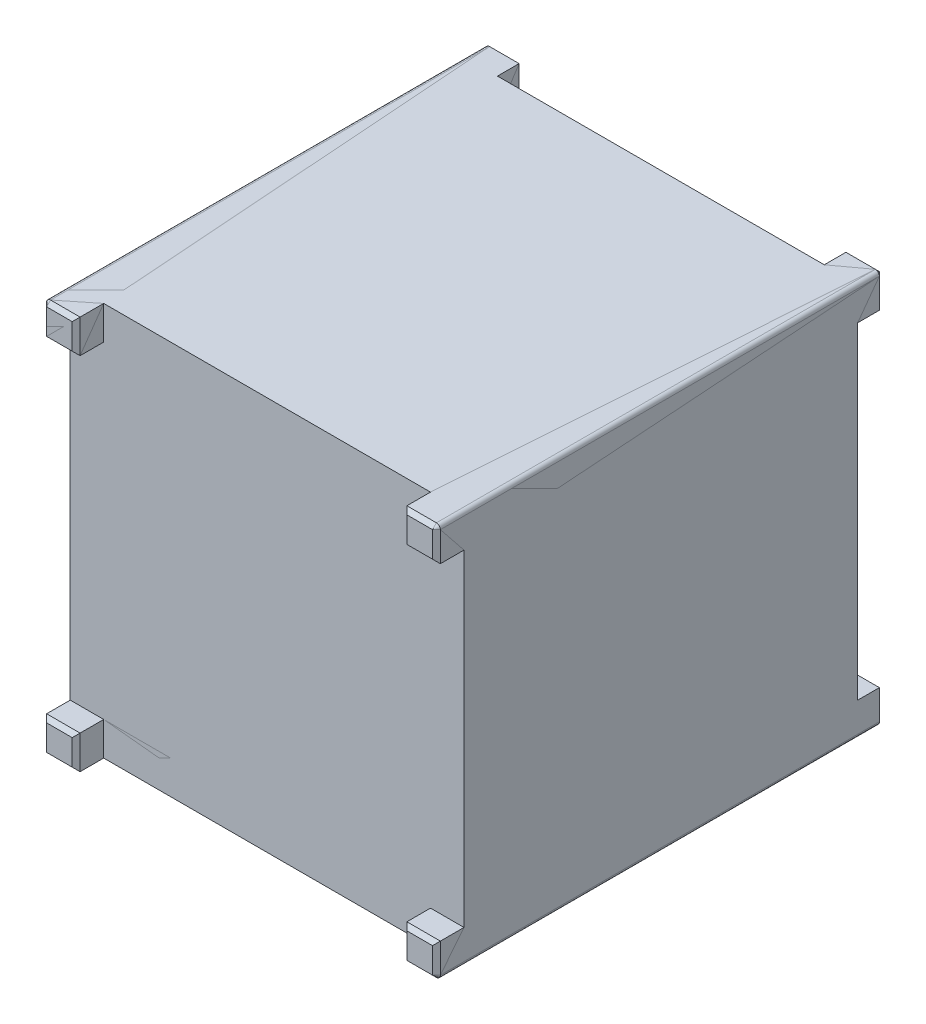
SolidWorks part; units mm, degrees
ref_plane "Front Plane" through (0, 0, 0) normal (0, 0, 1) x (1, 0, 0)
ref_plane "Top Plane" through (0, 0, 0) normal (0, 1, 0) x (1, 0, 0)
ref_plane "Right Plane" through (0, 0, 0) normal (1, 0, 0) x (0, 0, -1)
sketch "Sketch1" plane through (0, 0, 0) normal (0, 0, 1) x (1, 0, 0)
  line L1 (-50, -50) -> (50, -50) construction
  line L2 (-50, -50) -> (-50, 50) construction
  line L3 (-50, 50) -> (50, 50) construction
  line L4 (50, -50) -> (50, 50) construction
  line L5 (-50, -50) -> (50, 50) construction
  line L6 (-50, 50) -> (50, -50) construction
  line L23 (-50, 50) -> (-41.5, 50)
  line L24 (-50, 50) -> (-50, 41.5)
  line L25 (-50, 41.5) -> (-41.5, 41.5)
  line L26 (-41.5, 50) -> (-41.5, 41.5)
  line L27 (50, 50) -> (41.5, 50)
  line L28 (50, 50) -> (50, 41.5)
  line L29 (50, 41.5) -> (41.5, 41.5)
  line L30 (41.5, 50) -> (41.5, 41.5)
  line L31 (50, -50) -> (41.5, -50)
  line L32 (50, -50) -> (50, -41.5)
  line L33 (50, -41.5) -> (41.5, -41.5)
  line L34 (41.5, -50) -> (41.5, -41.5)
  line L35 (-50, -50) -> (-41.5, -50)
  line L36 (-50, -50) -> (-50, -41.5)
  line L37 (-50, -41.5) -> (-41.5, -41.5)
  line L38 (-41.5, -50) -> (-41.5, -41.5)
  point P0 (0, 0)
  dimension "D1" = 100
  dimension "D2" = 100
  dimension "D3" = 8.5
extrude "Boss-Extrude1" add sketch "Sketch1" along normal blind 56.75 and the other way blind 56.75
sketch "Sketch2" plane through (0, 0, 0) normal (0, 0, 1) x (1, 0, 0)
  line L1 (-50, -50) -> (50, -50)
  line L2 (-50, -50) -> (-50, 50)
  line L3 (-50, 50) -> (50, 50)
  line L4 (50, -50) -> (50, 50)
  line L5 (-50, -50) -> (50, 50) construction
  line L6 (-50, 50) -> (50, -50) construction
  point P0 (0, 0)
extrude "Boss-Extrude2" add sketch "Sketch2" along normal blind 49.75 and the other way blind 50.25
fillet "Fillet1" radius 1 4 edges at (50, -50, 0) (-50, -50, 0) (-50, 50, 0) (50, 50, 0)
chamfer "Chamfer2" distance 1 angle 45 40 edges at (-45.75, -41.5, 56.75) (-41.5, -45.75, 56.75) (-45.25, -50, 56.75) (-49.7071, -49.7071, 56.75) (-50, -45.25, 56.75) (41.5, -45.75, 56.75) (45.75, -41.5, 56.75) (50, -45.25, 56.75) (49.7071, -49.7071, 56.75) (45.25, -50, 56.75) (45.75, 41.5, 56.75) (41.5, 45.75, 56.75) (45.25, 50, 56.75) (49.7071, 49.7071, 56.75) (50, 45.25, 56.75) (-41.5, 45.75, 56.75) (-45.75, 41.5, 56.75) (-50, 45.25, 56.75) (-49.7071, 49.7071, 56.75) (-45.25, 50, 56.75) (41.5, 45.75, -56.75) (45.75, 41.5, -56.75) (50, 45.25, -56.75) (49.7071, 49.7071, -56.75) (45.25, 50, -56.75) (-45.75, 41.5, -56.75) (-41.5, 45.75, -56.75) (-45.25, 50, -56.75) (-49.7071, 49.7071, -56.75) (-50, 45.25, -56.75) (-41.5, -45.75, -56.75) (-45.75, -41.5, -56.75) (-50, -45.25, -56.75) (-49.7071, -49.7071, -56.75) (-45.25, -50, -56.75) (45.75, -41.5, -56.75) (41.5, -45.75, -56.75) (45.25, -50, -56.75) (49.7071, -49.7071, -56.75) (50, -45.25, -56.75)
surface "Surface-Offset1" parameters "D1"=0
equation "\"D1@Boss-Extrude1\"=113.5/2mm"
equation "\"D2@Boss-Extrude1\"=113.5/2"
